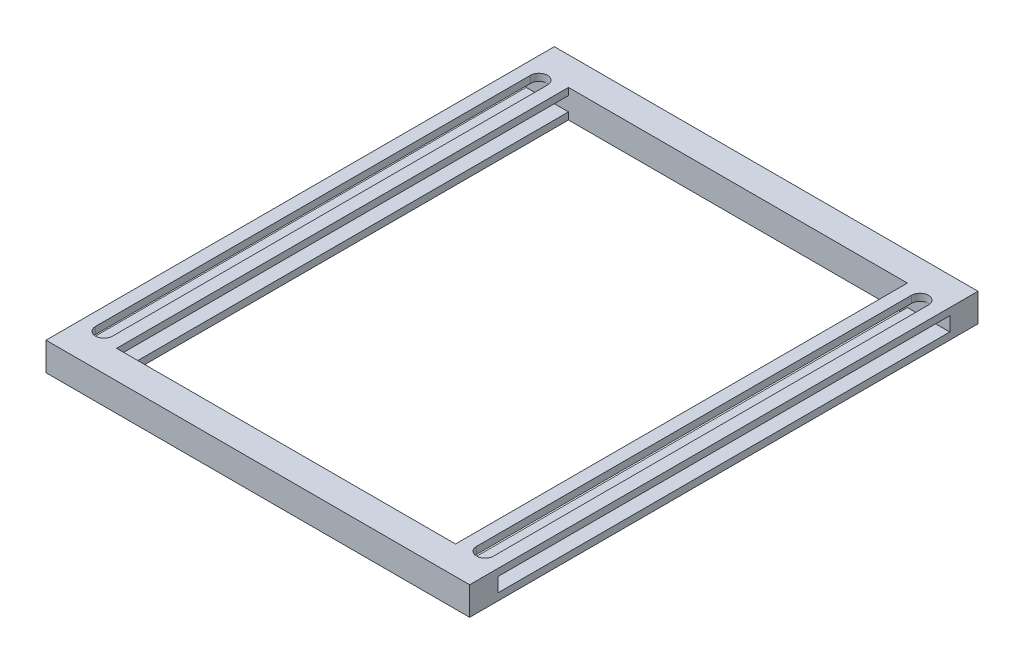
SolidWorks part; units mm, degrees
ref_plane "Front Plane" through (0, 0, 0) normal (0, 0, 1) x (1, 0, 0)
ref_plane "Top Plane" through (0, 0, 0) normal (0, 1, 0) x (1, 0, 0)
ref_plane "Right Plane" through (0, 0, 0) normal (1, 0, 0) x (0, 0, -1)
sketch "Sketch1" plane through (0, 0, 0) normal (0, 1, 0) x (1, 0, 0)
  line L0 (13.5831, -10.6058) -> (163.5831, -10.6058)
  line L1 (13.5831, -10.6058) -> (13.5831, 169.3942)
  line L3 (13.5831, 169.3942) -> (163.5831, 169.3942)
  line L4 (163.5831, 169.3942) -> (163.5831, -10.6058)
  line L9 (28.5831, 159.3942) -> (148.5831, 159.3942)
  line L11 (28.5831, -0.6058) -> (148.5831, -0.6058)
  line L13 (28.5831, -0.6058) -> (28.5831, 159.3942)
  line L15 (148.5831, 159.3942) -> (148.5831, -0.6058)
  line L17 (153.5831, 159.3942) -> (153.5831, -0.6058) construction
  line L18 (23.5831, -0.6058) -> (23.5831, 159.3942) construction
  line L19 (28.5831, 154.3942) -> (148.5831, 154.3942) construction
  line L20 (28.5831, 4.3942) -> (148.5831, 4.3942) construction
  line L21 (28.5831, 4.3942) -> (28.5831, 154.3942) construction
  line L22 (148.5831, 154.3942) -> (148.5831, 4.3942) construction
  line L23 (23.5831, 159.3942) -> (153.5831, 159.3942) construction
  line L24 (23.5831, -0.6058) -> (153.5831, -0.6058) construction
  dimension "D1" = 15
  dimension "D2" = 10
extrude "Boss-Extrude1" add sketch "Sketch1" along normal blind 10
sketch "Sketch2" plane through (0, 10, 0) normal (0, 1, 0) x (1, 0, 0)
  line L4 (21.1306, 156.3942) -> (21.1306, 2.3942) construction
  line L5 (24.1306, 156.3942) -> (24.1306, 2.3942)
  line L6 (18.1306, 156.3942) -> (18.1306, 2.3942)
  line L14 (156.0356, 156.3942) -> (156.0356, 2.3942) construction
  line L15 (153.0356, 156.3942) -> (153.0356, 2.3942)
  line L16 (159.0356, 156.3942) -> (159.0356, 2.3942)
  arc A0 (24.1306, 156.3942) -> (18.1306, 156.3942) centre (21.1306, 156.3942) ccw
  arc A1 (18.1306, 2.3942) -> (24.1306, 2.3942) centre (21.1306, 2.3942) ccw
  arc A4 (153.0356, 156.3942) -> (159.0356, 156.3942) centre (156.0356, 156.3942) cw
  arc A5 (159.0356, 2.3942) -> (153.0356, 2.3942) centre (156.0356, 2.3942) cw
  point P8 (21.1306, 79.3942)
  point P24 (156.0356, 79.3942)
extrude "Cut-Extrude1" cut sketch "Sketch2" against normal blind 7
sketch "Sketch3" plane through (13.5831, 0, 0) normal (-1, 0, 0) x (0, 0, 1)
  line L0 (-159.3942, 7.5) -> (-159.3942, 2.5)
  line L1 (0.6058, 7.5) -> (0.6058, 2.5)
  line L3 (-159.3942, 2.5) -> (0.6058, 2.5)
  line L4 (-159.3942, 7.5) -> (0.6058, 7.5)
extrude "Cut-Extrude2" cut sketch "Sketch3" against normal blind 200
